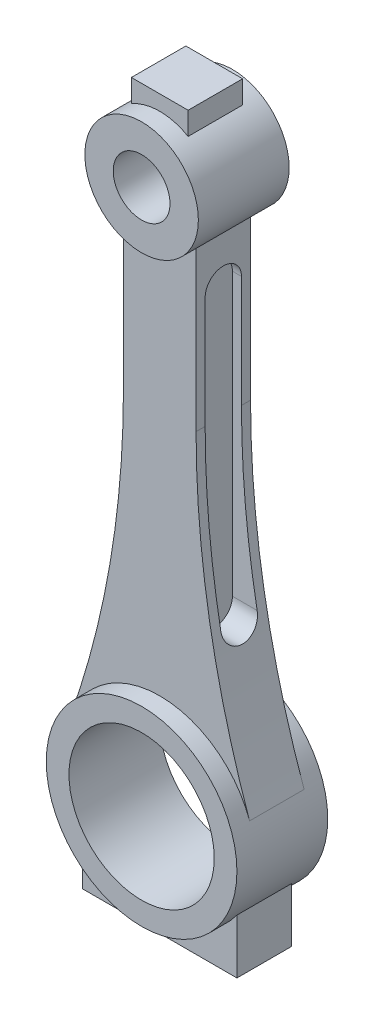
SolidWorks part; units mm, degrees
ref_plane "Front Plane" through (0, 0, 0) normal (0, 0, 1) x (1, 0, 0)
ref_plane "Top Plane" through (0, 0, 0) normal (0, 1, 0) x (1, 0, 0)
ref_plane "Right Plane" through (0, 0, 0) normal (1, 0, 0) x (0, 0, -1)
sketch "Sketch1" plane through (0, 0, 0) normal (0, 0, 1) x (1, 0, 0)
  line L0 (0, 120) -> (0, 0) construction
  line L1 (-8, 110.3953) -> (-8, 75.3953)
  line L2 (8, 110.3953) -> (8, 75.3953)
  line L3 (0, 0) -> (0, -49.4681) construction
  line L4 (-17, -12.3288) -> (-17, -24.3288)
  line L5 (-17, -24.3288) -> (17, -24.3288)
  line L6 (17, -24.3288) -> (17, -12.3288)
  line L7 (-6.25, 130.8253) -> (-6.25, 135.8253)
  line L8 (-6.25, 135.8253) -> (6.25, 135.8253)
  line L9 (6.25, 135.8253) -> (6.25, 130.8253)
  circle A0 centre (0, 0) radius 21
  circle A1 centre (0, 120) radius 12.5
  circle A2 centre (0, 0) radius 16
  circle A3 centre (0, 120) radius 6.25
  arc A4 (-8, 75.3953) -> (-19.7874, 7.0327) centre (-212.1328, 75.3953) cw
  arc A5 (8, 75.3953) -> (19.7874, 7.0327) centre (212.1328, 75.3953) ccw
  dimension "D2" = 42
  dimension "D3" = 32
  dimension "D4" = 25
  dimension "D5" = 12.5
  dimension "D1" = 120
  dimension "D6" = 8
  dimension "D7" = 35
  dimension "D8" = 34
  dimension "D9" = 12.5
  dimension "D10" = 5
  dimension "D11" = 12
extrude "Boss-Extrude1" add sketch "Sketch1" along normal mid plane 20 contours A0 A2 | A1 A3 region at (-12.1021, 121.0366, 0) region at (0, 20.406, 0)
extrude "Boss-Extrude2" add sketch "Sketch1<3>" along normal mid plane 12 contours A5 L2 A1 L1 A4 A0 | A1 L9 L8 L7 | A0 L4 L5 L6 region at (0, 57.8448, 0) region at (0, 133.8599, 0) region at (0, -21.3606, 0)
sketch "Sketch1<3>" plane through (0, 0, 0) normal (0, 0, 1) x (1, 0, 0) same geometry as "Sketch1"
sketch "Sketch2" plane through (0, 0, 0) normal (1, 0, 0) x (0, 0, -1)
  line L0 (0, 100) -> (0, 38) construction
  line L1 (4, 100) -> (4, 38)
  line L2 (-4, 100) -> (-4, 38)
  line L3 (-10, 132.5) -> (-10, 107.5) construction
  line L4 (-10, 132.5) -> (-10, 107.5)
  line L5 (-10, 120) -> (10, 120) construction
  line L6 (10, 107.5) -> (10, 132.5) construction
  arc A0 (4, 100) -> (-4, 100) centre (0, 100) ccw
  arc A1 (-4, 38) -> (4, 38) centre (0, 38) ccw
  point P3 (0, 69)
  dimension "D2" = 4
  dimension "D1" = 62
  dimension "D3" = 20
extrude "Cut-Extrude1" cut sketch "Sketch2" along normal through all from offset 6 contours L2 A1 L1 A0 region at (0, 69, 0)
mirror "Mirror1" about plane through (0, 0, 0) normal (1, 0, 0) of "Cut-Extrude1"
